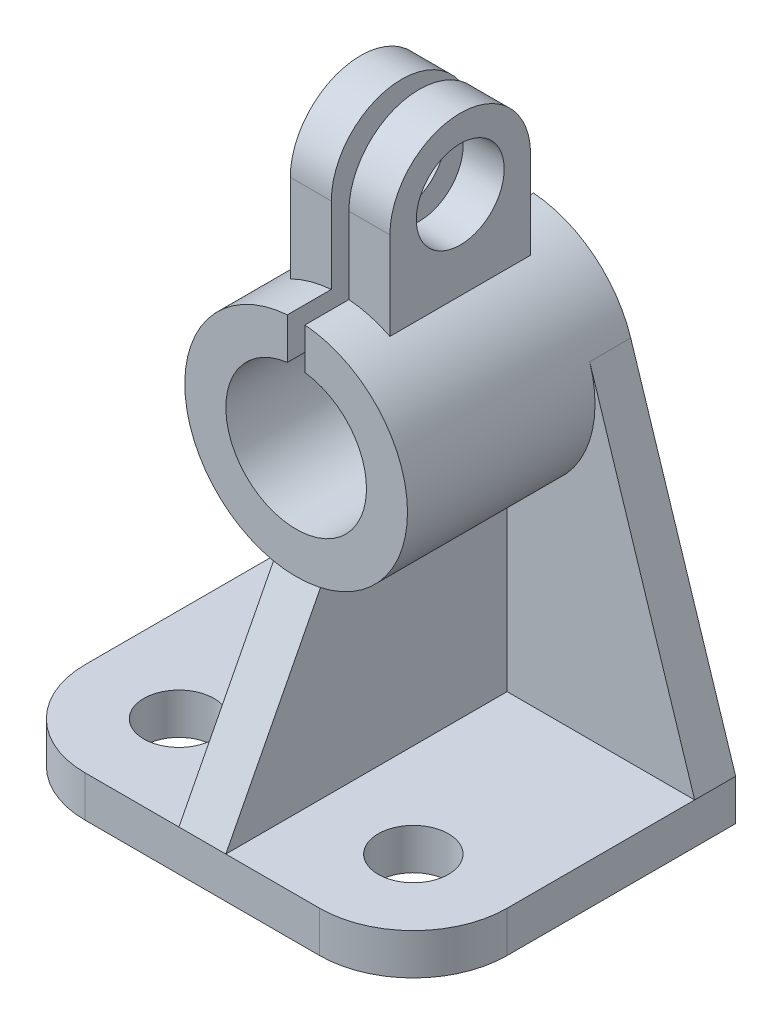
SolidWorks part; units mm, degrees
ref_plane "Front Plane" through (0, 0, 0) normal (0, 0, 1) x (1, 0, 0)
ref_plane "Top Plane" through (0, 0, 0) normal (0, 1, 0) x (1, 0, 0)
ref_plane "Right Plane" through (0, 0, 0) normal (1, 0, 0) x (0, 0, -1)
sketch "Sketch1" plane through (0, 0, 0) normal (0, 0, 1) x (1, 0, 0)
  line L0 (0, 0) -> (50000, 0) construction
  line L1 (0, 0) -> (0, 50000) construction
  line L2 (-18.0913, 59.3057) -> (-36, 3.5)
  line L3 (-36, -3.5) -> (36, -3.5)
  line L4 (-36, -3.5) -> (-36, 3.5)
  line L5 (-36, 3.5) -> (36, 3.5)
  line L6 (36, -3.5) -> (36, 3.5)
  line L7 (-36, -3.5) -> (36, 3.5) construction
  line L8 (-36, 3.5) -> (36, -3.5) construction
  line L9 (36, 3.5) -> (18.0913, 59.3057)
  line L10 (-1.5, 65.4059) -> (-1.5, 97.5)
  line L11 (-1.5, 97.5) -> (-8.5, 97.5)
  line L12 (-8.5, 97.5) -> (-8.5, 70.4926)
  line L13 (8.5, 97.5) -> (8.5, 70.4926)
  line L14 (1.5, 97.5) -> (8.5, 97.5)
  line L15 (1.5, 65.4059) -> (1.5, 97.5)
  circle A0 centre (0, 53.5) radius 12
  circle A1 centre (0, 53.5) radius 19
  point P5 (0, 0)
  dimension "D1" = 24
  dimension "D2" = 38
  dimension "D3" = 72
  dimension "D4" = 7
  dimension "D5" = 50
  dimension "D6" = 44
  dimension "D7" = 3
  dimension "D8" = 7
extrude "Boss-Extrude1" add sketch "Sketch1" along normal blind 55 contours L3 L6 L5 L4 region at (0, 0, 0)
extrude "Boss-Extrude2" add sketch "Sketch1<3>" along normal blind 7 contours A1 L2 L5 L9 region at (0, 21.2541, 0)
sketch "Sketch1<3>" plane through (0, 0, 0) normal (0, 0, 1) x (1, 0, 0) same geometry as "Sketch1"
extrude "Boss-Extrude3" add sketch "Sketch1<4>" along normal blind 39 contours A1 L15 A0 L10 region at (-14.0166, 65.5173, 0)
sketch "Sketch1<4>" plane through (0, 0, 0) normal (0, 0, 1) x (1, 0, 0) same geometry as "Sketch1"
extrude "Boss-Extrude4" add sketch "Sketch1<5>" along normal blind 24 from offset 7.5 contours A1 L13 L14 L15 | A1 L10 L11 L12 region at (-5.0437, 84.5986, 0) region at (5.0437, 84.5986, 0)
sketch "Sketch1<5>" plane through (0, 0, 0) normal (0, 0, 1) x (1, 0, 0) same geometry as "Sketch1"
fillet "Fillet1" 2 edges at (5, 97.5, 31.5) (5, 97.5, 7.5) type full round first side face at (5.0235, 84.5678, 31.5) second side face at (5.0235, 84.5678, 7.5) middle face at (5, 97.5, 19.5)
fillet "Fillet2" 2 edges at (-5, 97.5, 31.5) (-5, 97.5, 7.5) type full round first side face at (-5.0235, 84.5678, 31.5) second side face at (-5.0235, 84.5678, 7.5) middle face at (-5, 97.5, 19.5)
hole_wizard "Ø1.0mm Dowel Hole1" positions "Sketch2" profile "Sketch3" hole size "Ø1.0" standard "ANSI Metric" end condition through all
sketch "Sketch2" plane through (8.5, 0, 0) normal (1, 0, 0) x (0, 0, -1)
  line L0 (-31.5, 85.5) -> (-31.5, 70.4926) construction
  point P0 (-19.5, 85.5)
  point P3 (0, 0)
  point P7 (-22.2156, 85.4521)
  point P9 (0, 0)
  dimension "D1" = 12
sketch "Sketch3" plane through (8.5, 85.5, 19.5) normal (0, 1, 0) x (0, 0, -1)
  line L0 (0, 0) -> (0, 44.5)
  line L1 (0, 44.5) -> (7.5, 44.5)
  line L2 (7.5, 44.5) -> (7.5, 0)
  line L5 (7.5, 0) -> (0, 0)
  line L11 (0, -6.35) -> (0, 107.95) construction
  dimension "Thru Hole Dia." = 15
  dimension "Thru Hole Depth" = 44.5
sketch "Sketch4" plane through (0, 0, 0) normal (1, 0, 0) x (0, 0, -1)
  line L0 (-39, 34.5) -> (-55, 3.5)
  line L1 (-39, 72.4407) -> (-39, 34.5) construction
rib "Rib1" sketch "Sketch4" sketch "Sketch4" thickness 8 extrusion direction parallel to sketch draft on no parameters "D1"=8
fillet "Fillet3" radius 16 2 edges at (-36, 0, 55) (36, 0, 55)
hole_wizard "Ø12.0mm Dowel Hole1" positions "Sketch5" profile "Sketch6" hole size "Ø12.0" standard "ANSI Metric" end condition through all
sketch "Sketch5" plane through (0, 3.5, 0) normal (0, 1, 0) x (1, 0, 0)
  line L0 (36, -7) -> (18.0913, -7) construction
  line L1 (36, -39) -> (36, -7) construction
  line L2 (-36, -39) -> (-36, -7) construction
  point P0 (20, -39)
  point P2 (-20, -39)
  point P5 (0, 0)
  dimension "D1" = 32
  dimension "D2" = 16
  dimension "D3" = 16
sketch "Sketch6" plane through (20, 3.5, 39) normal (1, 0, 0) x (0, 0, 1)
  line L0 (0, 0) -> (0, 7)
  line L1 (0, 7) -> (6, 7)
  line L2 (6, 7) -> (6, 0)
  line L5 (6, 0) -> (0, 0)
  line L11 (0, -6.35) -> (0, 107.95) construction
  dimension "Thru Hole Dia." = 12
  dimension "Thru Hole Depth" = 7
